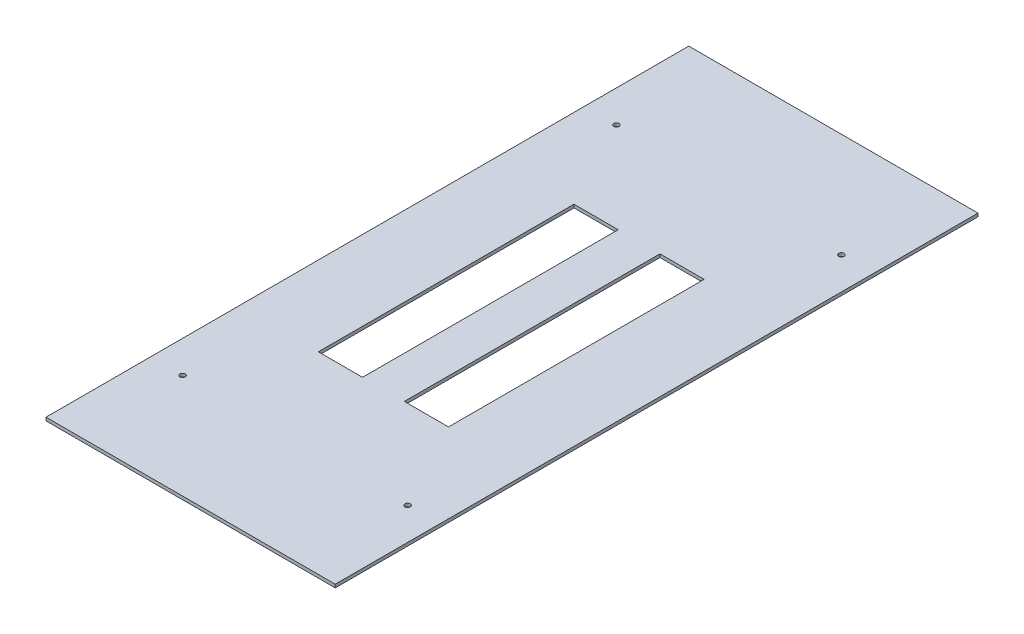
SolidWorks part; units mm, degrees
material "Acrylic (Medium-high impact)"
ref_plane "Front Plane" through (0, 0, 0) normal (0, 0, 1) x (1, 0, 0)
ref_plane "Top Plane" through (0, 0, 0) normal (0, 1, 0) x (1, 0, 0)
ref_plane "Right Plane" through (0, 0, 0) normal (1, 0, 0) x (0, 0, -1)
sketch "Sketch1" plane through (0, 0, 0) normal (0, 1, 0) x (1, 0, 0)
  line L0 (0, 212.5) -> (0, -212.5) construction
  line L1 (-115, 212.5) -> (115, 212.5)
  line L2 (-115, 212.5) -> (-115, -212.5)
  line L3 (-115, -212.5) -> (115, -212.5)
  line L4 (115, 212.5) -> (115, -212.5)
  line L5 (-115, 212.5) -> (115, -212.5) construction
  line L6 (-115, -212.5) -> (115, 212.5) construction
  line L8 (-115, 0) -> (115, 0) construction
  point P0 (0, 0)
  point P8 (-105, 202.5)
  point P14 (105, 202.5)
  point P16 (105, -202.5)
  point P17 (-105, -202.5)
  dimension "D1" = 210
  dimension "D2" = 405
  dimension "D3" = 10
  dimension "D4" = 10
extrude "Boss-Extrude1" add sketch "Sketch1" against normal blind 3 contours L1 L4 L3 L2
hole_wizard "Ø5.0 (4) Diameter Hole1" positions "Sketch2" profile "Sketch4" hole size "Ø5.0" standard "ANSI Metric" end condition through all
sketch "Sketch2" plane through (0, 0, 0) normal (0, 1, 0) x (1, 0, 0)
  point P0 (-105, 202.5)
  point P3 (105, 202.5)
  point P6 (105, -202.5)
  point P9 (-105, -202.5)
  point P13 (0, 0)
  point P14 (0, 0)
  point P15 (0, 0)
  point P16 (0, 0)
sketch "Sketch4" plane through (-105, 0, -202.5) normal (1, 0, 0) x (0, 0, 1)
  line L0 (0, 0) -> (0, 3)
  line L1 (0, 3) -> (2.5, 3)
  line L2 (2.5, 3) -> (2.5, 0)
  line L5 (2.5, 0) -> (0, 0)
  line L11 (0, -6.35) -> (0, 107.95) construction
  dimension "Thru Hole Dia." = 5
  dimension "Thru Hole Depth" = 3
sketch "Sketch5" plane through (0, 0, 0) normal (0, 1, 0) x (1, 0, 0)
  line L0 (0, 212.5) -> (0, -212.5) construction
  line L1 (-55.75, 113.6) -> (-24.5, 113.6) construction
  line L2 (-55.75, 113.6) -> (-55.75, -115) construction
  line L3 (-55.75, -115) -> (-24.5, -115) construction
  line L4 (-24.5, 113.6) -> (-24.5, -115) construction
  line L5 (24.5, 113.6) -> (24.5, -115) construction
  line L6 (-60.75, 118.6) -> (-19.5, 118.6)
  line L7 (-60.75, 118.6) -> (-60.75, -120)
  line L8 (-60.75, -120) -> (-19.5, -120)
  line L9 (-19.5, 118.6) -> (-19.5, -120)
  line L10 (55.75, -115) -> (24.5, -115) construction
  line L11 (55.75, 113.6) -> (55.75, -115) construction
  line L12 (55.75, 113.6) -> (24.5, 113.6) construction
  line L13 (19.5, 118.6) -> (19.5, -120)
  line L14 (60.75, -120) -> (19.5, -120)
  line L15 (60.75, 118.6) -> (60.75, -120)
  line L16 (60.75, 118.6) -> (19.5, 118.6)
  dimension "D1" = 88.9
  dimension "D2" = 228.6
  dimension "D3" = 55.75
  dimension "D4" = 5
  dimension "D5" = 5
  dimension "D6" = 5
  dimension "D7" = 5
  dimension "D8" = 24.5
extrude "Cut-Extrude1" cut sketch "Sketch5" against normal through all
sketch "Sketch6" plane through (0, 0, 0) normal (0, 1, 0) x (1, 0, 0)
  line L1 (-115, -212.5) -> (115, -212.5)
  line L2 (-115, -212.5) -> (-115, 212.5)
  line L3 (-115, 212.5) -> (115, 212.5)
  line L4 (115, -212.5) -> (115, 212.5)
  line L5 (-115, -212.5) -> (115, 212.5) construction
  line L6 (-115, 212.5) -> (115, -212.5) construction
  line L7 (-135, -300) -> (135, -300)
  line L8 (-135, -300) -> (-135, 300)
  line L9 (-135, 300) -> (135, 300)
  line L10 (135, -300) -> (135, 300)
  line L11 (-135, -300) -> (135, 300) construction
  line L12 (-135, 300) -> (135, -300) construction
  point P0 (0, 0)
  point P7 (0, 0)
  dimension "D1" = 270
  dimension "D2" = 600
extrude "Boss-Extrude3" add sketch "Sketch6" against normal up to surface (3 mm away) up to face at (-40.125, -3, 0.7)
